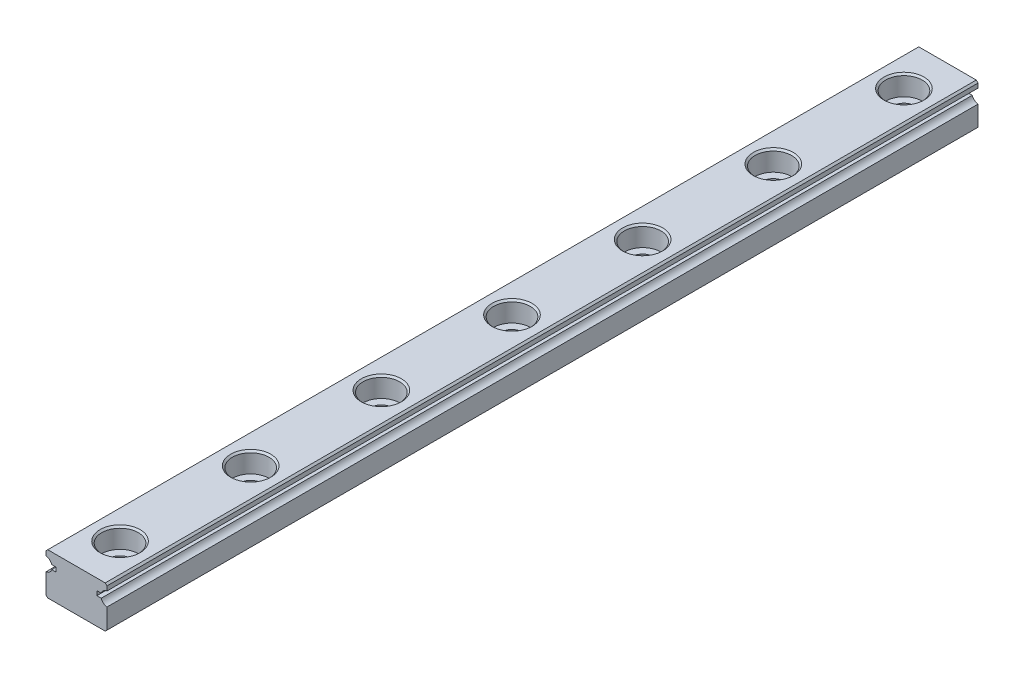
SolidWorks part; units mm, degrees
ref_plane "Спереди" through (0, 0, 0) normal (0, 0, 1) x (1, 0, 0)
ref_plane "Сверху" through (0, 0, 0) normal (0, 1, 0) x (1, 0, 0)
ref_plane "Справа" through (0, 0, 0) normal (1, 0, 0) x (0, 0, -1)
sketch "Sketch1" plane through (0, 0, 0) normal (0, 0, 1) x (1, 0, 0)
  line L0 (0, 0) -> (0, 4.3706) construction
  line L1 (-3.3, -2.4) -> (3.3, -2.4)
  line L2 (-3.5, -2.2) -> (-3.5, 0.1063)
  line L3 (-3.3, 2.4) -> (3.3, 2.4)
  line L4 (3.5, -2.2) -> (3.5, 0.1063)
  line L5 (-3.5, -2.4) -> (3.5, 2.4) construction
  line L6 (-3.5, 2.4) -> (3.5, -2.4) construction
  line L7 (-3.5, 1.6937) -> (-3.5, 2.2)
  line L8 (3.5, 1.6937) -> (3.5, 2.2)
  line L9 (-3.5, -2.2) -> (-3.3, -2.4)
  line L10 (3.3, -2.4) -> (3.5, -2.2)
  line L11 (3.3, 2.4) -> (3.5, 2.2)
  line L12 (-3.5, 2.2) -> (-3.3, 2.4)
  line L13 (2.8401, 0.65) -> (2.3401, 0.65)
  line L14 (-2.8401, 0.65) -> (-2.3401, 0.65)
  line L15 (2.3401, 0.65) -> (2.3401, 1.15)
  line L16 (-2.8401, 1.15) -> (-2.3401, 1.15)
  line L17 (-2.3401, 0.65) -> (-2.3401, 1.15)
  line L18 (2.8401, 1.15) -> (2.3401, 1.15)
  arc A0 (-3.5, 1.6937) -> (-2.8401, 1.15) centre (-3.6, 0.9) cw
  arc A1 (3.5, 1.6937) -> (2.8401, 1.15) centre (3.6, 0.9) ccw
  arc A2 (-2.8401, 0.65) -> (-3.5, 0.1063) centre (-3.6, 0.9) cw
  arc A3 (2.8401, 0.65) -> (3.5, 0.1063) centre (3.6, 0.9) ccw
  point P0 (0, 0)
  dimension "D4" = 0.8
  dimension "D5" = 0.1
  dimension "D1" = 7
  dimension "D2" = 4.8
  dimension "D3" = 1.5
  dimension "D6" = 0.5
  dimension "D7" = 0.5
extrude "Extrude1" add sketch "Sketch1" along normal blind 100
sketch "Sketch2" plane through (0, 2.4, 0) normal (0, 1, 0) x (1, 0, 0)
  line L0 (0, 0) -> (0, -5) construction
  circle A0 centre (0, -5) radius 1.2
  circle A1 centre (0, -5) radius 2.1
  dimension "D1" = 2.4
  dimension "D2" = 4.2
  dimension "D3" = 5
extrude "Extrude2" cut sketch "Sketch2" against normal up to next contours A0 region at (0, 2.4, 5)
extrude "Extrude4" cut sketch "Sketch" against normal blind 2.3
sketch "Sketch" plane through (0, 2.4, 0) normal (0, 1, 0) x (1, 0, 0) same geometry as "Sketch2"
chamfer "Chamfer1" distance 0.2 angle 45 2 edges at (0, -2.4, 6.2) (0, 2.4, 7.1)
pattern_linear "LPattern1" count 7 spacing 15 along (0, 0, 1) of "Extrude4", "Chamfer1", "Extrude2"
